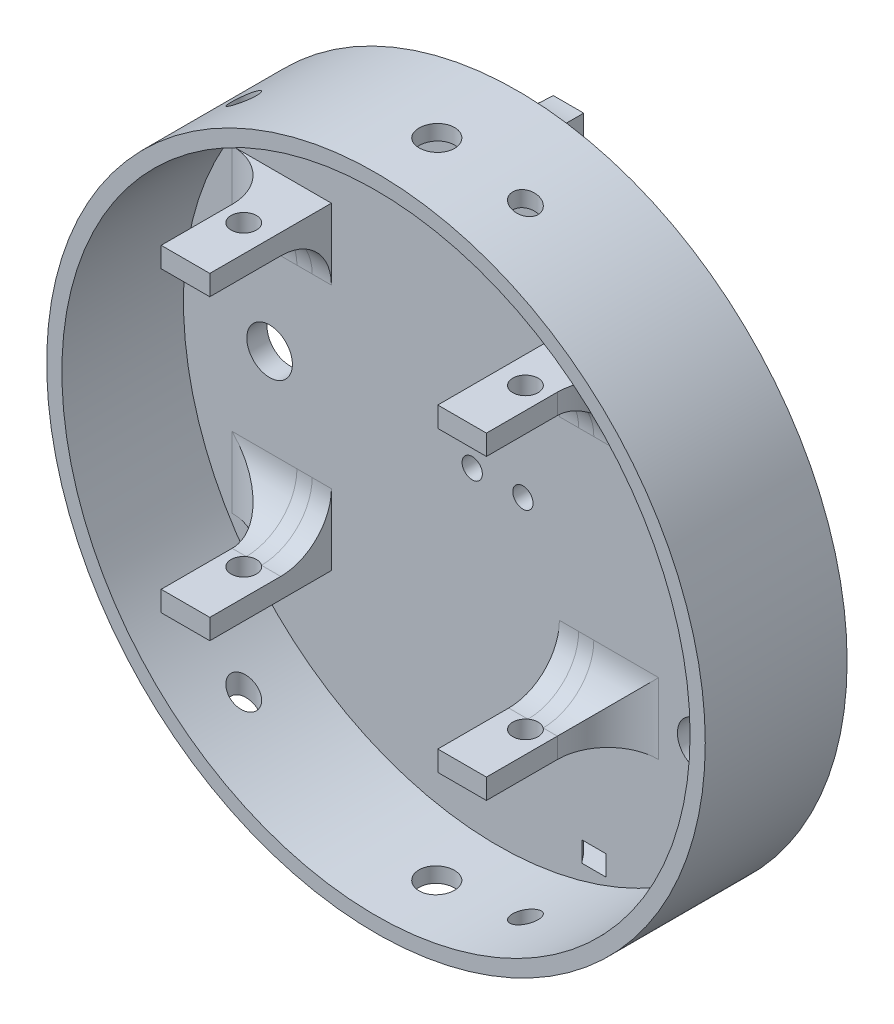
SolidWorks part; units mm, degrees
ref_plane "Alzado" through (0, 0, 0) normal (0, 0, 1) x (1, 0, 0)
ref_plane "Planta" through (0, 0, 0) normal (0, 1, 0) x (1, 0, 0)
ref_plane "Vista lateral" through (0, 0, 0) normal (1, 0, 0) x (0, 0, -1)
sketch "Croquis1" plane through (0, 0, 0) normal (0, 0, 1) x (1, 0, 0)
  line L0 (10, 20) -> (-10, 20) construction
  circle A0 centre (0, 0) radius 32.5
  circle A1 centre (-2.5, 0) radius 1
  circle A2 centre (2.5, 0) radius 1
  circle A3 centre (0, 20) radius 1
  circle A4 centre (10, 20) radius 1
  circle A5 centre (-10, 20) radius 1
  point P9 (0, 20)
  dimension "D1" = 65
  dimension "D4" = 2
  dimension "D7" = 2
  dimension "D2" = 2.5
  dimension "D3" = 2.5
  dimension "D5" = 20
  dimension "D6" = 20
extrude "Saliente-Extruir1" add sketch "Croquis1" along normal blind 2
sketch "Croquis2" plane through (0, 0, 2) normal (0, 0, 1) x (1, 0, 0)
  line L0 (-21.2, -15.7) -> (-16.4, -15.7)
  line L1 (10.9, -15.7) -> (6.1, -15.7)
  line L2 (-21.2, -15.7) -> (-21.2, -13.7)
  line L3 (-21.2, -13.7) -> (-16.4, -13.7)
  line L4 (-16.4, -13.7) -> (-16.4, -15.7)
  line L5 (6.1, -15.7) -> (6.1, -13.7)
  line L6 (6.1, -13.7) -> (10.9, -13.7)
  line L7 (10.9, -13.7) -> (10.9, -15.7)
  line L8 (6.1, -15.7) -> (10.9, -15.7)
  line L9 (0, 0) -> (12.8027, 0) construction
  line L10 (10.9, 13.7) -> (10.9, 15.7)
  line L11 (10.9, 15.7) -> (6.1, 15.7)
  line L12 (6.1, 13.7) -> (10.9, 13.7)
  line L13 (6.1, 15.7) -> (6.1, 13.7)
  line L14 (-16.4, 13.7) -> (-16.4, 15.7)
  line L15 (-21.2, 15.7) -> (-16.4, 15.7)
  line L16 (-21.2, 15.7) -> (-21.2, 13.7)
  line L17 (-21.2, 13.7) -> (-16.4, 13.7)
  point P2 (0, -15.7)
  point P3 (-16.4, -15.7)
  point P13 (8.5, -15.7)
  point P16 (8.5, 15.7)
  dimension "D1" = 32.1
  dimension "D2" = 10.9
  dimension "D3" = 15.7
  dimension "D4" = 4.8
  dimension "D5" = 4.8
  dimension "D6" = 2
  dimension "D7" = 2
extrude "Saliente-Extruir2" add sketch "Croquis2" along normal blind 12 contours L7 L6 L5 L1 | L4 L3 L2 L0 | L16 L17 L14 L15 | L11 L13 L12 L10 region at (-18.8, -14.7, 2) region at (8.5, -14.7, 2) region at (8.5, 14.7, 2) region at (-18.8, 14.7, 2)
sketch "Croquis3" plane through (0, -15.7, 0) normal (0, -1, 0) x (1, 0, 0)
  line L0 (-21.2, 14) -> (-21.2, 2) construction
  line L3 (10.9, 14) -> (10.9, 2) construction
  line L6 (-21.2, 2) -> (-16.4, 2) construction
  circle A0 centre (-19.05, 8) radius 1.25
  circle A1 centre (8.75, 8) radius 1.25
  point P6 (0, 0)
  dimension "D1" = 2.5
  dimension "D2" = 2.15
  dimension "D3" = 2.15
  dimension "D4" = 6
extrude "Cortar-Extruir1" cut sketch "Croquis3" against normal up to surface (31.4 mm away) up to face at (8.5, 15.7, 8)
ref_plane "Plano1" through (0, -32.5, 0) normal (0, -1, 0) x (-1, 0, 0)
ref_plane "Plano2" through (0, -28.35, 0) normal (0, -1, 0) x (-1, 0, 0)
sketch "Croquis5" plane through (0, -28.35, 0) normal (0, -1, 0) x (-1, 0, 0)
  line L0 (-8.75, -8) -> (19.05, -8) construction
  line L1 (0, 0) -> (0, -8) construction
  line L2 (-32.5, -2) -> (32.5, -2) construction
  line L3 (-10.68, -2) -> (-8.3104, -2)
  line L4 (32.5, 0) -> (-32.5, 0) construction
  line L5 (9.277, 0) -> (6.408, 0)
  line L6 (8.3104, -2) -> (10.68, -2)
  line L7 (-6.408, 0) -> (-9.277, 0)
  arc A0 (-9.277, 0) -> (-10.68, -2) centre (0, -8) ccw
  arc A1 (-6.408, 0) -> (-8.3104, -2) centre (0, -8) ccw
  arc A2 (10.68, -2) -> (9.277, 0) centre (0, -8) ccw
  arc A3 (8.3104, -2) -> (6.408, 0) centre (0, -8) ccw
  dimension "D1" = 24.5
  dimension "D2" = 20.5
extrude "Cortar-Extruir3" cut sketch "Croquis5" against normal blind 2
mirror "Simetría1" about plane through (0, 0, 0) normal (0, 1, 0) of "Cortar-Extruir3"
sketch "Croquis6" plane through (0, 0, 0) normal (0, 0, -1) x (-1, 0, 0)
  circle A0 centre (-20, 12.5) radius 2.25
  circle A1 centre (-20, -12.5) radius 2.25
  circle A2 centre (22.5, 0) radius 2.25
  dimension "D1" = 4.5
  dimension "D2" = 4.5
  dimension "D3" = 4.5
  dimension "D6" = 25
  dimension "D7" = 12.5
  dimension "D4" = 22.5
  dimension "D5" = 20
extrude "Cortar-Extruir4" cut sketch "Croquis6" against normal blind 2.5
sketch "Croquis7" plane through (0, 0, 2) normal (0, 0, 1) x (1, 0, 0)
  circle A2 centre (0, 0) radius 32.5 construction
  circle A9 centre (0, 0) radius 32.5
  circle A11 centre (0, 0) radius 31
  dimension "D1" = 1.5
extrude "Saliente-Extruir3" add sketch "Croquis7" along normal blind 12
ref_plane "Plano3" through (0, -32.5, 0) normal (0, -1, 0) x (-1, 0, 0)
sketch "Croquis8" plane through (0, -32.5, 0) normal (0, -1, 0) x (-1, 0, 0)
  circle A0 centre (-8.75, -8) radius 1.25 construction
  circle A1 centre (-8.75, -8) radius 1.25
  circle A2 centre (19.05, -8) radius 1.25 construction
  circle A3 centre (19.05, -8) radius 1.25
  circle A4 centre (0, -8) radius 1.75
  dimension "D1" = 3.5
extrude "Cortar-Extruir5" cut sketch "Croquis8" against normal blind 70
sketch "Sketch1" plane through (0, 0, 0) normal (0, 0, -1) x (-1, 0, 0)
  line L0 (6.408, 26.35) -> (6.408, 28.35) construction
  line L1 (-1.502, 28.85) -> (1.498, 28.85)
  line L2 (-1.502, 28.85) -> (-1.502, 25.85)
  line L3 (-1.502, 25.85) -> (1.498, 25.85)
  line L4 (1.498, 28.85) -> (1.498, 25.85)
  line L5 (-1.502, 28.85) -> (1.498, 25.85) construction
  line L6 (-1.502, 25.85) -> (1.498, 28.85) construction
  line L7 (0, 0) -> (-11.4103, 0) construction
  line L8 (-1.502, -25.85) -> (1.498, -28.85) construction
  line L9 (-1.502, -28.85) -> (1.498, -25.85) construction
  line L10 (1.498, -28.85) -> (1.498, -25.85)
  line L11 (-1.502, -25.85) -> (1.498, -25.85)
  line L12 (-1.502, -28.85) -> (-1.502, -25.85)
  line L13 (-1.502, -28.85) -> (1.498, -28.85)
  line L14 (-6.408, -26.35) -> (-6.408, -28.35) construction
  point P0 (-0.002, 27.35)
  point P8 (6.408, 27.35)
  point P15 (-0.002, -27.35)
  dimension "D1" = 4.91
  dimension "D2" = 3
  dimension "D3" = 3
  dimension "D4" = 4.906
extrude "Boss-Extrude1" add sketch "Sketch1" along normal blind 5
fillet "Fillet1" radius 2 6 edges at (1.502, 27.35, 0) (-1.498, -27.35, 0) (0.002, 25.85, 0) (0.002, 28.85, 0) (0.002, -25.85, 0) (0.002, -28.85, 0) second distance 5 first distance on face at (0.002, 27.35, 0)
sketch "Sketch2" plane through (0, 0, 2) normal (0, 0, 1) x (1, 0, 0)
  line L1 (-10.68, -26.35) -> (-5.6668, -26.35)
  line L2 (-10.68, -26.35) -> (-10.68, -28.75)
  line L3 (-10.68, -28.75) -> (-5.6668, -28.75)
  line L4 (-5.6668, -26.35) -> (-5.6668, -28.75)
  line L5 (10.68, 26.35) -> (5.4941, 26.35)
  line L6 (10.68, 26.35) -> (10.68, 28.75)
  line L7 (10.68, 28.75) -> (5.4941, 28.75)
  line L8 (5.4941, 26.35) -> (5.4941, 28.75)
extrude "Tapon" add sketch "Sketch2" against normal up to surface (2 mm away) up to face at (1.002, 25.6, 0)
fillet "Fillet4" radius 5 8 edges at (-21.2, 14.7, 2) (-21.2, -14.7, 2) (-18.8, -13.7, 2) (-18.8, 13.7, 2) (10.9, 14.7, 2) (8.5, 13.7, 2) (8.5, -13.7, 2) (10.9, -14.7, 2)
equation "\"D2@Croquis6\"=\"D1@Croquis6\""
equation "\"D3@Croquis6\"=\"D1@Croquis6\""
equation "\"D7@Croquis6\"=\"D6@Croquis6\"/2"
